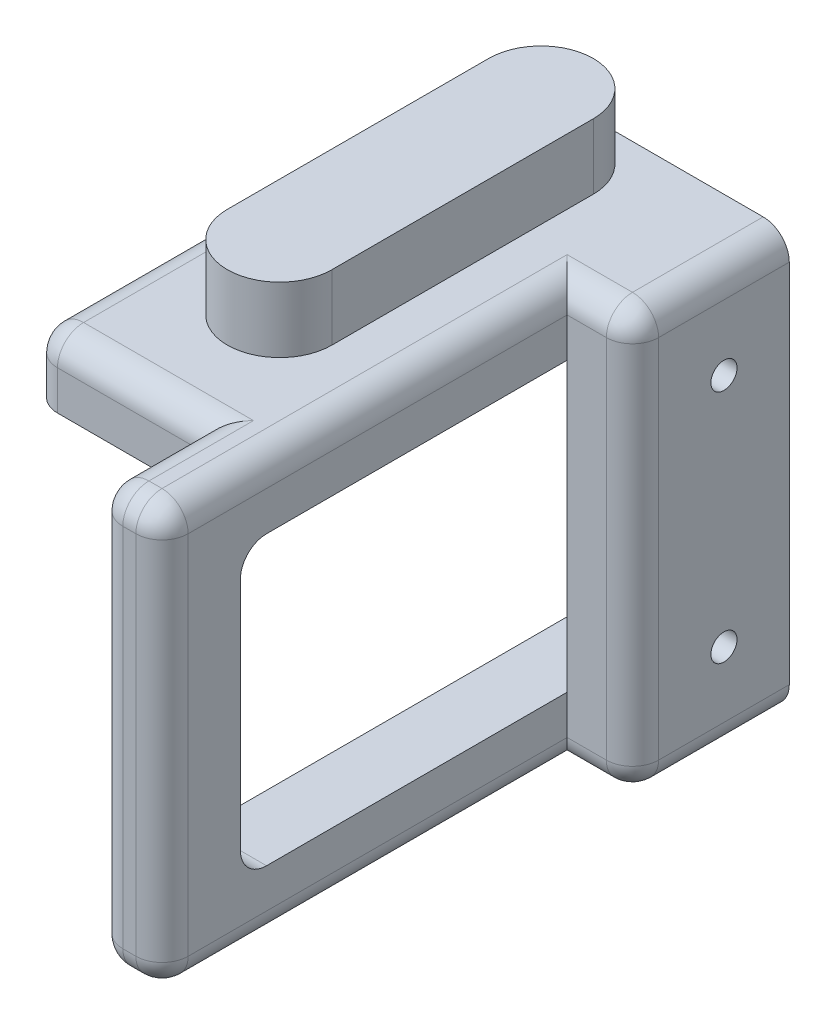
SolidWorks part; units mm, degrees
ref_plane "Front Plane" through (0, 0, 0) normal (0, 0, 1) x (1, 0, 0)
ref_plane "Top Plane" through (0, 0, 0) normal (0, 1, 0) x (1, 0, 0)
ref_plane "Right Plane" through (0, 0, 0) normal (1, 0, 0) x (0, 0, -1)
sketch "Sketch1" plane through (0, 0, 0) normal (1, 0, 0) x (0, 0, -1)
  line L0 (0, 22) -> (0, 27)
  line L1 (0, 0) -> (-35, 0)
  line L3 (0, 22) -> (-35, 22)
  line L4 (-37, 2) -> (-37, 20)
  line L5 (0, 27) -> (-41, 27)
  line L6 (-43, 25) -> (-43, -3)
  line L7 (-41, -5) -> (0, -5)
  line L8 (0, -5) -> (0, 0)
  arc A0 (-41, -5) -> (-43, -3) centre (-41, -3) cw
  arc A1 (-41, 27) -> (-43, 25) centre (-41, 25) ccw
  arc A2 (-37, 2) -> (-35, 0) centre (-35, 2) ccw
  arc A3 (-37, 20) -> (-35, 22) centre (-35, 20) cw
  point P15 (-37, 0)
  point P18 (-37, 22)
  dimension "D5" = 2
  dimension "D6" = 2
  dimension "D1" = 37
  dimension "D2" = 22
  dimension "D3" = 5
  dimension "D4" = 6
extrude "Boss-Extrude1" add sketch "Sketch1" against normal blind 5
sketch "Sketch2" plane through (0, 0, 0) normal (1, 0, 0) x (0, 0, -1)
  line L0 (0, 27) -> (-41, 27) construction
  line L1 (0, -5) -> (-12, -5)
  line L2 (0, -5) -> (0, 27)
  line L3 (0, 27) -> (-12, 27)
  line L4 (-12, -5) -> (-12, 27)
  dimension "D1" = 12
extrude "Boss-Extrude2" add sketch "Sketch2" along normal blind 5
sketch "Sketch3" plane through (5, 0, 0) normal (1, 0, 0) x (0, 0, -1)
  line L0 (-5, 22) -> (-5, 0) construction
  line L1 (-12, 22) -> (0, 22) construction
  line L2 (-12, 22) -> (-12, 0) construction
  line L3 (-12, 0) -> (0, 0) construction
  line L4 (0, 22) -> (0, 0) construction
  line L5 (-5, 11) -> (0, 11) construction
  circle A0 centre (-5, 2) radius 1
  circle A1 centre (-5, 20) radius 1
  dimension "D2" = 2
  dimension "D1" = 5
  dimension "D3" = 2
extrude "Cut-Extrude1" cut sketch "Sketch3" against normal up to next
fillet "Fillet1" radius 2 2 edges at (5, 27, 6) (5, -5, 6)
sketch "Sketch5" plane through (-5, 0, 0) normal (-1, 0, 0) x (0, 0, 1)
  line L0 (35, 22) -> (0, 22) construction
  line L5 (0, 27) -> (35, 27)
  line L6 (0, 27) -> (0, 22)
  line L7 (0, 22) -> (35, 22)
  line L8 (35, 27) -> (35, 22)
  arc A0 (37, 20) -> (35, 22) centre (35, 20) ccw construction
extrude "Boss-Extrude3" add sketch "Sketch5" along normal blind 13
fillet "Fillet2" radius 2 1 edges at (-18, 24.5, 35)
fillet "Fillet3" radius 2 15 edges at (-5, 27, 38) (-5, 26.4142, 42.4142) (-5, 11, 43) (-5, -5, 20.5) (0, 27, 26.5) (0, 26.4142, 42.4142) (0, 11, 43) (0, -5, 26.5) (1.5, 27, 12) (4.4142, 26.4142, 12) (1.5, -5, 12) (4.4142, -4.4142, 12) (-5, -4.4142, 42.4142) (0, -4.4142, 42.4142) (5, 11, 12)
fillet "Fillet4" radius 2 3 edges at (-18, 27, 16.5) (-17.4142, 27, 34.4142) (-9.5, 27, 35)
sketch "Encastre" plane through (0, 27, 0) normal (0, 1, 0) x (1, 0, 0)
  line L0 (-9, -5) -> (-9, -25) construction
  line L1 (-5, -5) -> (-5, -25)
  line L2 (-13, -5) -> (-13, -25)
  line L3 (-16, 0) -> (3, 0) construction
  line L4 (-2, -41) -> (-2, -10) construction
  arc A0 (-5, -5) -> (-13, -5) centre (-9, -5) ccw
  arc A1 (-13, -25) -> (-5, -25) centre (-9, -25) ccw
  point P2 (-9, -15)
  dimension "D5" = 4
  dimension "D1" = 20
  dimension "D2" = 8
  dimension "D3" = 5
  dimension "D4" = 3
extrude "Boss-Extrude4" add sketch "Encastre" along normal blind 5
